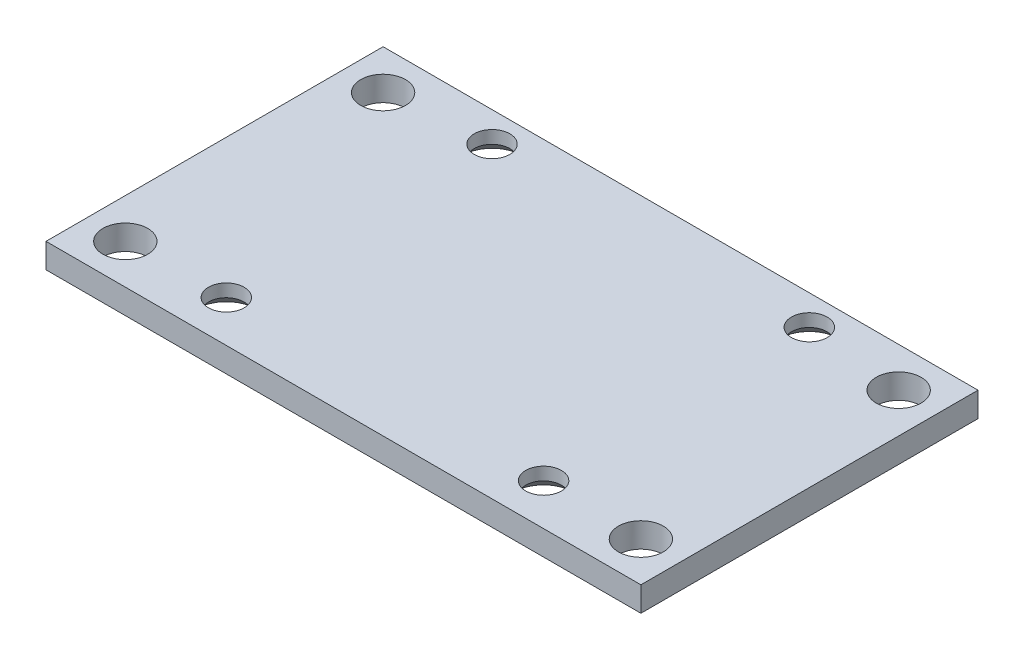
SolidWorks part; units mm, degrees
ref_plane "Front Plane" through (0, 0, 0) normal (0, 0, 1) x (1, 0, 0)
ref_plane "Top Plane" through (0, 0, 0) normal (0, 1, 0) x (1, 0, 0)
ref_plane "Right Plane" through (0, 0, 0) normal (1, 0, 0) x (0, 0, -1)
sketch "Sketch1" plane through (0, 0, 0) normal (0, 1, 0) x (1, 0, 0)
  line L1 (-15, -8.5) -> (15, -8.5)
  line L2 (-15, -8.5) -> (-15, 8.5)
  line L3 (-15, 8.5) -> (15, 8.5)
  line L4 (15, -8.5) -> (15, 8.5)
  line L5 (-15, -8.5) -> (15, 8.5) construction
  line L6 (-15, 8.5) -> (15, -8.5) construction
  point P0 (0, 0)
  dimension "D1" = 30
  dimension "D2" = 17
extrude "Boss-Extrude1" add sketch "Sketch1" along normal blind 1.2446
hole_wizard "M1.6 Clearance Hole1" positions "Sketch3" profile "Sketch4" countersink size "M2" standard "Ansi Metric" end condition through all
sketch "Sketch3" plane through (0, 0, 0) normal (0, -1, 0) x (1, 0, 0)
  point P1 (-8, 6.4071)
  point P4 (8, 6.4071)
  point P7 (-8, -6.9929)
  point P10 (8, -6.9929)
sketch "Sketch4" plane through (-8, 0, 6.4071) normal (1, 0, 0) x (0, 0, -1)
  line L0 (0, 0) -> (0, 1.2446)
  line L1 (0, 1.2446) -> (0.9, 1.2446)
  line L2 (0.9, 1.2446) -> (0.9, 0.6)
  line L3 (0.9, 0.6) -> (1.5, 0)
  line L5 (1.5, 0) -> (0, 0)
  line L6 (-0.9, 0.6) -> (-1.5, 0) construction
  line L11 (0, -6.35) -> (0, 107.95) construction
  dimension "Thru Hole Dia." = 1.8
  dimension "Thru Hole Depth" = 1.2446
  dimension "Near C'Sink Dia." = 3
  dimension "Near C'Sink Angle" = 90
hole_wizard "#2 Clearance Hole1" positions "Sketch6" profile "Sketch5" hole size "#2" standard "Ansi Inch"
sketch "Sketch6" plane through (0, 1.2446, 0) normal (0, 1, 0) x (-1, 0, 0)
  line L0 (11, -4.4929) -> (11, -8.2929) construction
  line L1 (-11, -8.2929) -> (-11, 7.7071) construction
  line L2 (-15, -8.5) -> (15, -8.5) construction
  line L3 (15, 8.5) -> (-15, 8.5) construction
  point P0 (13, -6.5)
  point P1 (13, 6.5)
  point P3 (-13, -6.5)
  point P5 (-13, 6.5)
  dimension "D1" = 2
  dimension "D2" = 2
  dimension "D3" = 2
  dimension "D4" = 2
sketch "Sketch5" plane through (-13, 1.2446, -6.5) normal (1, 0, 0) x (0, 0, 1)
  line L0 (0, 0) -> (0, 2.7112)
  line L1 (0, 2.7112) -> (1.1303, 2.032)
  line L2 (1.1303, 2.032) -> (1.1303, 0)
  line L5 (1.1303, 0) -> (0, 0)
  line L10 (0, 2.7112) -> (-1.1303, 2.032) construction
  line L11 (0, -6.35) -> (0, 107.95) construction
  dimension "Hole Dia." = 2.2606
  dimension "Hole Depth" = 2.032
  dimension "Drill Angle" = 118
